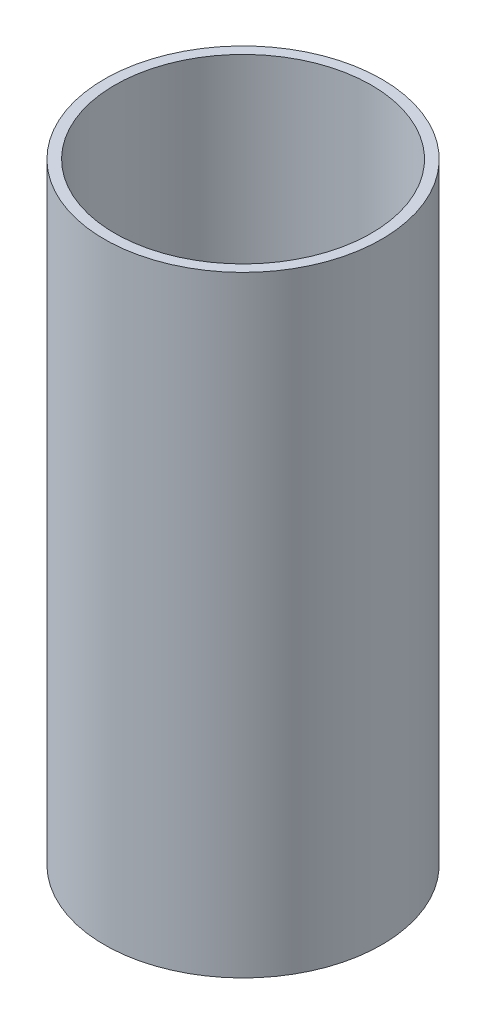
SolidWorks part; units mm, degrees
ref_plane "Front Plane" through (0, 0, 0) normal (0, 0, 1) x (1, 0, 0)
ref_plane "Top Plane" through (0, 0, 0) normal (0, 1, 0) x (1, 0, 0)
ref_plane "Right Plane" through (0, 0, 0) normal (1, 0, 0) x (0, 0, -1)
sketch "Sketch1" plane through (0, 0, 0) normal (0, 1, 0) x (1, 0, 0)
  circle A0 centre (0, 0) radius 109.5375
  circle A1 centre (0, 0) radius 101.3587
  dimension "D1" = 219.075
  dimension "D2" = 202.7174
extrude "Extrude1" add sketch "Sketch1" along normal blind 482.6
equation "\"D2@Sketch1\" = \"D1@Sketch1\" - .322*2"
